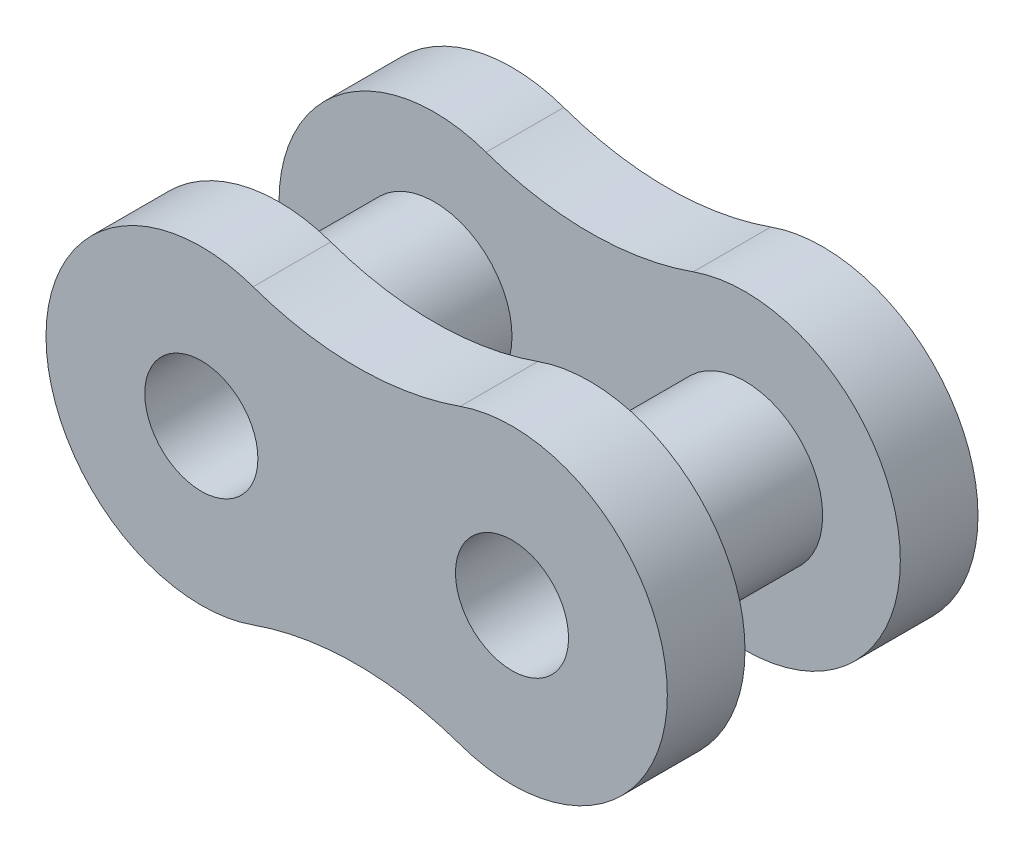
SolidWorks part; units mm, degrees
ref_plane "Front Plane" through (0, 0, 0) normal (0, 0, 1) x (1, 0, 0)
ref_plane "Top Plane" through (0, 0, 0) normal (0, 1, 0) x (1, 0, 0)
ref_plane "Right Plane" through (0, 0, 0) normal (1, 0, 0) x (0, 0, -1)
sketch "Sketch1" plane through (0, 0, 0) normal (0, 0, 1) x (1, 0, 0)
  line L0 (6.35, 0) -> (0, 0) construction
  circle A0 centre (0, 0) radius 1.1557
  circle A1 centre (6.35, 0) radius 1.1557
  circle A2 centre (0, 0) radius 1.5875
  circle A3 centre (6.35, 0) radius 1.5875
  arc A6 (1.0583, -2.9934) -> (1.0583, 2.9934) centre (0, 0) cw
  arc A7 (5.2917, -2.9934) -> (5.2917, 2.9934) centre (6.35, 0) ccw
  arc A8 (1.0583, 2.9934) -> (5.2917, 2.9934) centre (3.175, 8.9803) ccw
  arc A9 (1.0583, -2.9934) -> (5.2917, -2.9934) centre (3.175, -8.9803) cw
  point P13 (3.175, 0)
  dimension "D2" = 2.3114
  dimension "D3" = 2.3114
  dimension "D4" = 3.175
  dimension "D5" = 3.175
  dimension "D6" = 3.175
  dimension "D7" = 3.175
  dimension "D8" = 6.35
  dimension "D9" = 6.35
  dimension "D1" = 6.35
extrude "Boss-Extrude1" add sketch "Sketch1" along normal blind 1.5875 contours A6 A9 A7 A8 A3 A2 | A3 | A2 | A1 | A0 region at (3.175, 0, 0)
extrude "Boss-Extrude2" add sketch "Sketch1<3>" against normal blind 3.175 contours A3 | A2 | A1 | A0
sketch "Sketch1<3>" plane through (0, 0, 0) normal (0, 0, 1) x (1, 0, 0) same geometry as "Sketch1"
sketch "Sketch2" plane through (0, 0, -3.175) normal (0, 0, -1) x (-1, 0, 0)
  arc A0 (-1.0583, 2.9934) -> (-1.0583, -2.9934) centre (0, 0) cw
  arc A1 (-5.2917, 2.9934) -> (-5.2917, -2.9934) centre (-6.35, 0) ccw
  arc A2 (-5.2917, 2.9934) -> (-1.0583, 2.9934) centre (-3.175, 8.9803) ccw
  arc A3 (-1.0583, -2.9934) -> (-5.2917, -2.9934) centre (-3.175, -8.9803) ccw
  circle A4 centre (-6.35, 0) radius 1.1557
  circle A5 centre (0, 0) radius 1.1557
  dimension "D1" = 2.3114
  dimension "D2" = 2.3114
  dimension "D3" = 3.175
extrude "Boss-Extrude3" add sketch "Sketch2" along normal blind 1.5875
